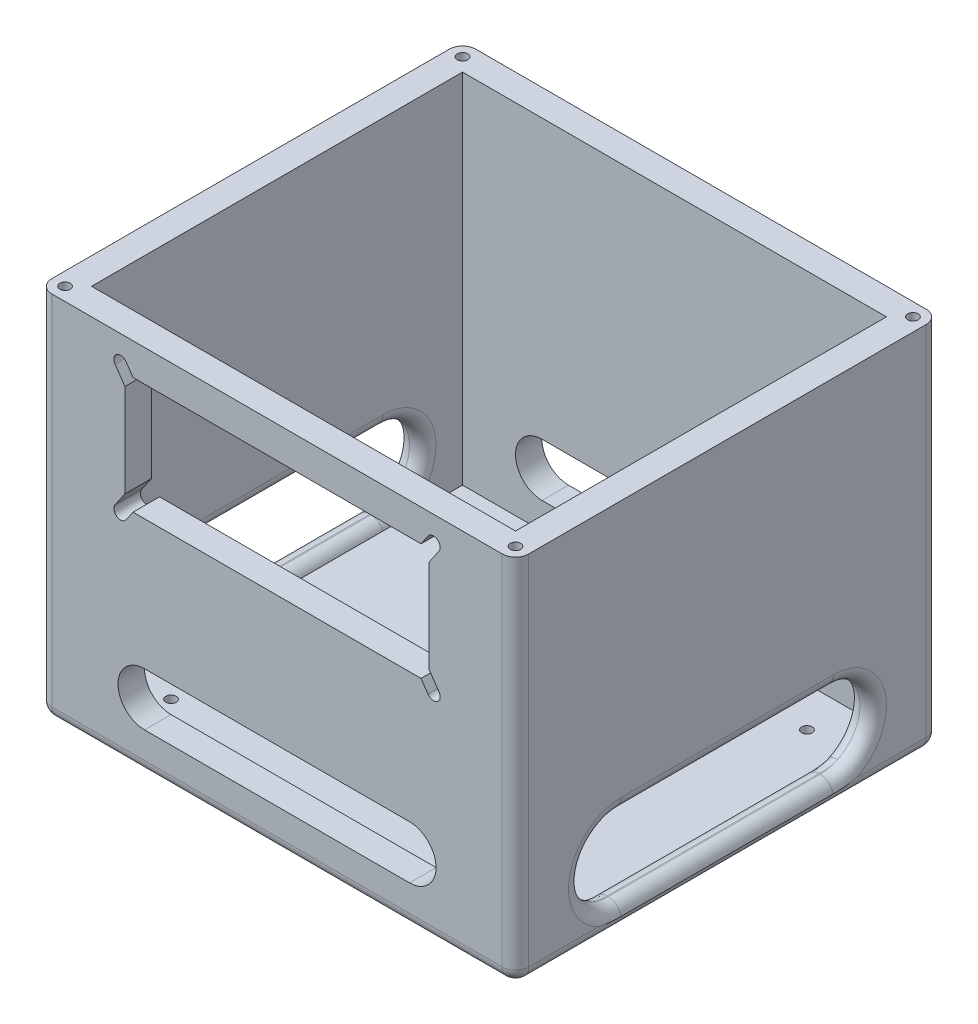
SolidWorks part; units mm, degrees
ref_plane "Front Plane" through (0, 0, 0) normal (0, 0, 1) x (1, 0, 0)
ref_plane "Top Plane" through (0, 0, 0) normal (0, 1, 0) x (1, 0, 0)
ref_plane "Right Plane" through (0, 0, 0) normal (1, 0, 0) x (0, 0, -1)
sketch "Sketch1" plane through (0, 0, 0) normal (0, 1, 0) x (1, 0, 0)
  line L1 (57.15, -50.8) -> (-57.15, -50.8)
  line L2 (57.15, -50.8) -> (57.15, 50.8)
  line L3 (57.15, 50.8) -> (-57.15, 50.8)
  line L4 (-57.15, -50.8) -> (-57.15, 50.8)
  line L5 (0, 50.8) -> (0, -50.8) construction
  line L6 (57.15, 0) -> (-57.15, 0) construction
  point P0 (0, 0)
  dimension "D1" = 101.6
  dimension "4in" = 114.3
extrude "Boss-Extrude1" add sketch "Sketch1" along normal blind 88.9
sketch "Sketch2" plane through (0, 88.9, 0) normal (0, 1, 0) x (1, 0, 0)
  line L1 (50.8, -44.45) -> (-50.8, -44.45)
  line L2 (50.8, -44.45) -> (50.8, 44.45)
  line L3 (50.8, 44.45) -> (-50.8, 44.45)
  line L4 (-50.8, -44.45) -> (-50.8, 44.45)
  line L5 (0, 44.45) -> (0, -44.45) construction
  line L6 (50.8, 0) -> (-50.8, 0) construction
  point P0 (0, 0)
  dimension "D1" = 88.9
  dimension "D2" = 101.6
extrude "Cut-Extrude1" cut sketch "Sketch2" against normal blind 85.725
hole_wizard "M3x0.5 Tapped Hole1" positions "Sketch3" profile "Sketch4" tap size "M3x0.5" standard "ANSI Metric" end condition through all
sketch "Sketch3" plane through (0, 0, 0) normal (0, -1, 0) x (-1, 0, 0)
  point P0 (41.275, -34.925)
  point P2 (-41.275, -34.925)
  point P4 (-41.275, 34.925)
  point P6 (41.275, 34.925)
  dimension "D1" = 82.55
  dimension "D2" = 69.85
  dimension "D3" = 41.275
  dimension "D4" = 34.925
sketch "Sketch4" plane through (-41.275, 0, 34.925) normal (1, 0, 0) x (0, 0, -1)
  line L0 (0, 0) -> (0, 88.9)
  line L1 (0, 88.9) -> (1.25, 88.9)
  line L2 (1.25, 88.9) -> (1.25, 0)
  line L5 (1.25, 0) -> (0, 0)
  line L11 (0, -6.35) -> (0, 107.95) construction
  dimension "Thru Tap Drill Dia." = 2.5
  dimension "Thru Tap Drill Depth" = 88.9
cosmetic thread "Hole Thread1" parameters "D2"=3
cosmetic thread "Hole Thread2" parameters "D2"=3
cosmetic thread "Hole Thread3" parameters "D2"=3
cosmetic thread "Hole Thread4" parameters "D2"=3
hole_wizard "M3x0.5 Tapped Hole2" positions "Sketch5" profile "Sketch6" tap size "M3x0.5" standard "ANSI Metric"
sketch "Sketch5" plane through (0, 88.9, 0) normal (0, 1, 0) x (1, 0, 0)
  line L0 (57.15, 50.8) -> (-57.15, 50.8) construction
  line L1 (-57.15, 50.8) -> (-57.15, -50.8) construction
  line L2 (-57.15, -50.8) -> (57.15, -50.8) construction
  line L3 (57.15, -50.8) -> (57.15, 50.8) construction
  point P0 (-53.975, 47.625)
  point P2 (53.975, 47.625)
  point P4 (53.975, -47.625)
  point P6 (-53.975, -47.625)
  dimension "D1" = 3.175
  dimension "D2" = 3.175
  dimension "D3" = 3.175
  dimension "D4" = 3.175
cosmetic thread "Hole Thread5" parameters "D1"=6.35, "D2"=3
cosmetic thread "Hole Thread6" parameters "D1"=6.35, "D2"=3
cosmetic thread "Hole Thread7" parameters "D1"=6.35, "D2"=3
cosmetic thread "Hole Thread8" parameters "D1"=6.35, "D2"=3
sketch "Sketch6" plane through (-53.975, 88.9, -47.625) normal (1, 0, 0) x (0, 0, 1)
  line L0 (0, 0) -> (0, 7.1011)
  line L1 (0, 7.1011) -> (1.25, 6.35)
  line L2 (1.25, 6.35) -> (1.25, 0)
  line L5 (1.25, 0) -> (0, 0)
  line L10 (0, 7.1011) -> (-1.25, 6.35) construction
  line L11 (0, -6.35) -> (0, 107.95) construction
  dimension "Tap Drill Dia." = 2.5
  dimension "Tap Drill Depth" = 6.35
  dimension "Drill Angle" = 118
sketch "Sketch7" plane through (0, 0, 50.8) normal (0, 0, 1) x (1, 0, 0)
  line L0 (-57.15, 88.9) -> (57.15, 88.9) construction
  line L1 (36.449, 53.34) -> (-36.449, 53.34)
  line L2 (36.449, 53.34) -> (36.449, 81.28)
  line L3 (36.449, 81.28) -> (-36.449, 81.28)
  line L4 (-36.449, 53.34) -> (-36.449, 81.28)
  line L5 (0, 81.28) -> (0, 53.34) construction
  line L6 (36.449, 67.31) -> (-36.449, 67.31) construction
  circle A0 centre (-37.5, 82.81) radius 1.6
  circle A1 centre (37.5, 82.81) radius 1.6
  circle A2 centre (37.5, 51.81) radius 1.6
  circle A3 centre (-37.5, 51.81) radius 1.6
  point P0 (0, 67.31)
  point P7 (0, 88.9)
  dimension "D3" = 3.2
  dimension "D1" = 72.898
  dimension "D2" = 7.62
  dimension "27.5mm" = 27.94
  dimension "D4" = 15.5
  dimension "D5" = 37.5
extrude "Cut-Extrude2" cut sketch "Sketch7" against normal blind 73.025
sketch "Sketch8" plane through (0, 0, -50.8) normal (0, 0, -1) x (-1, 0, 0)
  line L0 (-31.75, 15.875) -> (31.75, 15.875) construction
  line L1 (-31.75, 22.225) -> (31.75, 22.225)
  line L2 (-31.75, 9.525) -> (31.75, 9.525)
  line L3 (-57.15, 0) -> (57.15, 0) construction
  arc A0 (-31.75, 22.225) -> (-31.75, 9.525) centre (-31.75, 15.875) ccw
  arc A1 (31.75, 9.525) -> (31.75, 22.225) centre (31.75, 15.875) ccw
  point P2 (0, 15.875)
  point P11 (0, 0)
  dimension "D2" = 6.35
  dimension "D1" = 63.5
  dimension "D3" = 9.525
extrude "Cut-Extrude3" cut sketch "Sketch8" against normal through all both and the other way through all
sketch "Sketch9" plane through (-57.15, 0, 0) normal (-1, 0, 0) x (0, 0, 1)
  line L0 (25.4, 14.605) -> (-25.4, 14.605) construction
  line L1 (25.4, 5.08) -> (-25.4, 5.08)
  line L2 (25.4, 24.13) -> (-25.4, 24.13)
  line L3 (-50.8, 0) -> (50.8, 0) construction
  arc A0 (25.4, 5.08) -> (25.4, 24.13) centre (25.4, 14.605) ccw
  arc A1 (-25.4, 24.13) -> (-25.4, 5.08) centre (-25.4, 14.605) ccw
  point P2 (0, 14.605)
  dimension "D2" = 9.525
  dimension "D1" = 50.8
  dimension "D3" = 5.08
extrude "Cut-Extrude4" cut sketch "Sketch9" against normal through all both and the other way through all
sketch "Sketch10" plane through (0, 0, 50.8) normal (0, 0, 1) x (1, 0, 0)
  line L0 (-37.5, 82.81) -> (-34.5419, 78.5038) construction
  line L1 (-36.1812, 83.7159) -> (-33.2231, 79.4097)
  line L2 (-38.8188, 81.9041) -> (-35.8607, 77.5978)
  line L3 (0, -48.895) -> (0, 48.895) construction
  line L4 (37.5, 82.81) -> (34.5419, 78.5038) construction
  line L5 (36.1812, 83.7159) -> (33.2231, 79.4097)
  line L6 (38.8188, 81.9041) -> (35.8607, 77.5978)
  line L7 (-36.449, 67.31) -> (36.449, 67.31) construction
  line L8 (-36.449, 81.28) -> (-36.449, 53.34) construction
  line L9 (36.449, 53.34) -> (36.449, 81.28) construction
  line L10 (-37.5, 51.81) -> (-34.5419, 56.1162) construction
  line L11 (-36.1812, 50.9041) -> (-33.2231, 55.2103)
  line L12 (-38.8188, 52.7159) -> (-35.8607, 57.0222)
  line L13 (37.5, 51.81) -> (34.5419, 56.1162) construction
  line L14 (36.1812, 50.9041) -> (33.2231, 55.2103)
  line L15 (38.8188, 52.7159) -> (35.8607, 57.0222)
  arc A0 (-36.1812, 83.7159) -> (-38.8188, 81.9041) centre (-37.5, 82.81) ccw
  arc A1 (-35.8607, 77.5978) -> (-33.2231, 79.4097) centre (-34.5419, 78.5038) ccw
  circle A2 centre (-37.5, 82.81) radius 1.6 construction
  arc A3 (36.1812, 83.7159) -> (38.8188, 81.9041) centre (37.5, 82.81) cw
  arc A4 (35.8607, 77.5978) -> (33.2231, 79.4097) centre (34.5419, 78.5038) cw
  arc A5 (-36.1812, 50.9041) -> (-38.8188, 52.7159) centre (-37.5, 51.81) cw
  arc A6 (-35.8607, 57.0222) -> (-33.2231, 55.2103) centre (-34.5419, 56.1162) cw
  arc A7 (36.1812, 50.9041) -> (38.8188, 52.7159) centre (37.5, 51.81) ccw
  arc A8 (35.8607, 57.0222) -> (33.2231, 55.2103) centre (34.5419, 56.1162) ccw
  point P3 (-36.021, 80.6569)
  point P15 (36.021, 80.6569)
  point P28 (-36.021, 53.9631)
  point P35 (36.021, 53.9631)
  dimension "D1" = 4.3062
extrude "Cut-Extrude5" cut sketch "Sketch10" against normal up to next
fillet "Fillet1" radius 3.175 22 edges at (-50.8, 14.605, 34.925) (-50.8, 14.605, -34.925) (50.8, 14.605, 34.925) (50.8, 24.13, 0) (-57.15, 14.605, 34.925) (-57.15, 5.08, 0) (-57.15, 14.605, -34.925) (57.15, 14.605, 34.925) (57.15, 5.08, 0) (57.15, 14.605, -34.925) (-50.8, 24.13, 0) (50.8, 14.605, -34.925) (-57.15, 24.13, 0) (57.15, 24.13, 0) (-57.15, 44.45, -50.8) (57.15, 44.45, -50.8) (57.15, 44.45, 50.8) (-57.15, 44.45, 50.8) (-57.15, 0, 0) (0, 0, -50.8) (57.15, 0, 0) (0, 0, 50.8)
